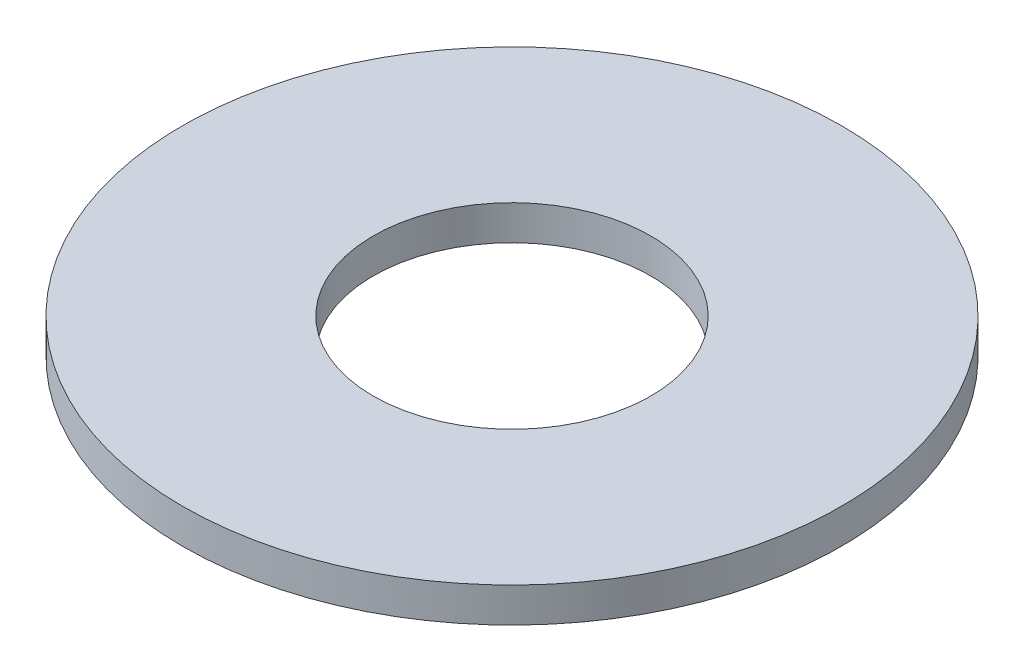
SolidWorks part; units mm, degrees
ref_plane "Front Plane" through (0, 0, 0) normal (0, 0, 1) x (1, 0, 0)
ref_plane "Top Plane" through (0, 0, 0) normal (0, 1, 0) x (1, 0, 0)
ref_plane "Right Plane" through (0, 0, 0) normal (1, 0, 0) x (0, 0, -1)
sketch "Sketch1" plane through (0, 0, 0) normal (0, 1, 0) x (1, 0, 0)
  circle A0 centre (0, 0) radius 47.5
  dimension "FLANGE_OD" = 95
extrude "Boss-Extrude1" add sketch "Sketch1" along normal blind 5
sketch "Sketch2" plane through (0, 0, 0) normal (0, 1, 0) x (1, 0, 0)
  circle A0 centre (0, 0) radius 20
  dimension "BORE_D" = 40
extrude "Cut-Extrude1" cut sketch "Sketch2" along normal through all
sketch "Sketch3" plane through (0, 5, 0) normal (0, 1, 0) x (1, 0, 0)
  circle A0 centre (0, 0) radius 12.6258 construction
  circle A1 centre (-12.6258, 0) radius 4.0636
  dimension "BOLT_D" = 8.1271
  dimension "BOLT_PCD" = 25.2515
extrude "Cut-Extrude2" cut sketch "Sketch3" against normal blind 3.395 rebuild error yes
pattern_circular "CirPattern1" count 4 over 360 rebuild error yes
